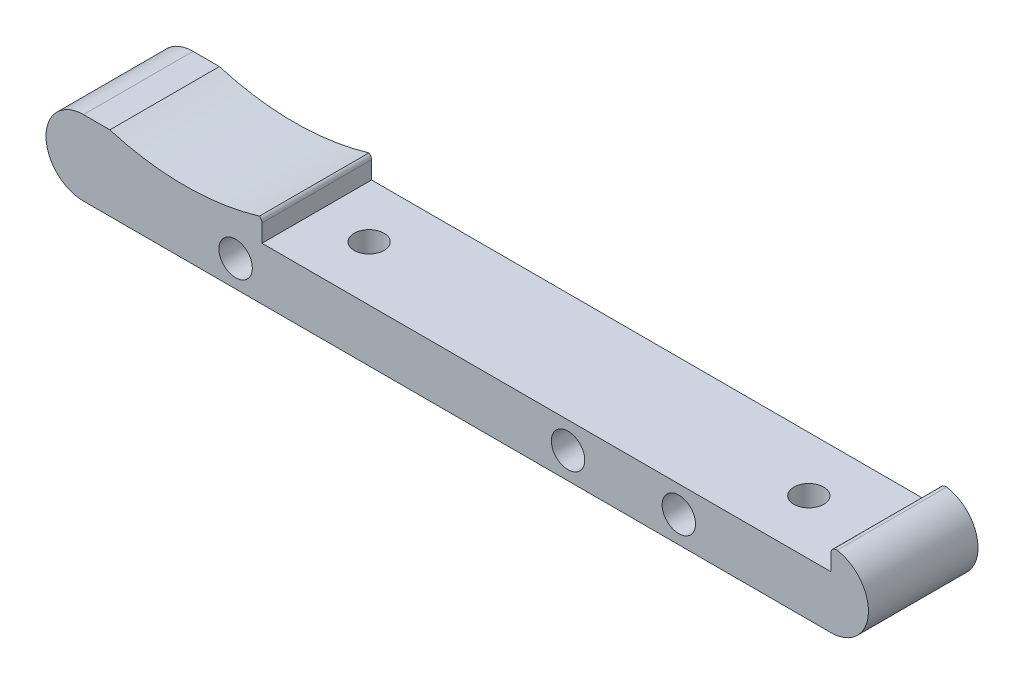
SolidWorks part; units mm, degrees
ref_plane "Front Plane" through (0, 0, 0) normal (0, 0, 1) x (1, 0, 0)
ref_plane "Top Plane" through (0, 0, 0) normal (0, 1, 0) x (1, 0, 0)
ref_plane "Right Plane" through (0, 0, 0) normal (1, 0, 0) x (0, 0, -1)
sketch "Sketch1" plane through (0, 0, 0) normal (0, 0, 1) x (1, 0, 0)
  line L0 (53.975, 7.62) -> (53.975, 0) construction
  line L2 (0, 7.62) -> (0, 0) construction
  line L3 (0, 0) -> (107.95, 0) construction
  line L4 (107.95, 7.62) -> (107.95, 0) construction
  line L6 (0, 0) -> (107.95, 0)
  line L9 (21.971, 3.81) -> (37.973, 3.81) construction
  line L10 (37.973, 3.81) -> (69.977, 3.81) construction
  line L11 (69.977, 3.81) -> (85.979, 3.81) construction
  line L12 (107.95, 10.8204) -> (107.95, 7.62)
  line L13 (53.975, 3.81) -> (107.95, 3.81) construction
  line L14 (0, 10.8204) -> (25.781, 10.8204)
  line L15 (25.781, 10.8204) -> (25.781, 7.62)
  line L16 (25.781, 7.62) -> (107.95, 7.62)
  circle A5 centre (21.971, 3.81) radius 2.413
  circle A6 centre (37.973, 3.81) radius 2.413 construction
  circle A7 centre (69.977, 3.81) radius 2.413
  circle A8 centre (85.979, 3.81) radius 2.413
  arc A9 (0, 10.8204) -> (0, 0) centre (0, 5.4102) ccw
  arc A10 (107.95, 10.8204) -> (107.95, 0) centre (107.95, 5.4102) cw
  point P0 (53.975, 3.81)
  dimension "D3" = 3.2004
  dimension "D4" = 16.002
  dimension "D5" = 4.826
  dimension "D2" = 32.004
  dimension "D1" = 53.975
  dimension "D7" = 82.169
  dimension "D8" = 7.62
extrude "Boss-Extrude1" add sketch "Sketch1" along normal blind 15.8242
sketch "Sketch3" plane through (0, 7.62, 0) normal (0, 1, 0) x (1, 0, 0)
  line L0 (96.8375, -7.9121) -> (11.1125, -7.9121) construction
  line L1 (53.975, -15.8242) -> (53.975, 0) construction
  line L4 (0, 0) -> (107.95, 0) construction
  line L5 (0, -15.8242) -> (107.95, -15.8242) construction
  circle A0 centre (96.8375, -7.9121) radius 2.159
  circle A3 centre (33.3375, -7.9121) radius 2.159
  point P8 (53.975, -7.9121)
  dimension "D1" = 4.318
  dimension "D2" = 85.725
  dimension "D3" = 22.225
extrude "Cut-Extrude1" cut sketch "Sketch3" against normal up to surface (7.62 mm away) up to face at (53.975, 0, 7.9121)
sketch "Sketch4" plane through (0, 0, 0) normal (0, 0, -1) x (-1, 0, 0)
  line L0 (-3.81, 10.8204) -> (-25.4, 10.8204)
  line L1 (-25.781, 10.8204) -> (0, 10.8204) construction
  arc A0 (-3.81, 10.8204) -> (-25.4, 10.8204) centre (-14.605, 46.9297) cw
  dimension "D2" = 37.6884
  dimension "D1" = 21.59
extrude "Cut-Extrude2" cut sketch "Sketch4" against normal up to surface (15.8242 mm away) up to face at (53.6303, 6.8145, 15.8242)
fillet "Fillet1" radius 0.762 2 edges at (107.95, 10.8204, 7.9121) (25.781, 10.8204, 7.9121)
